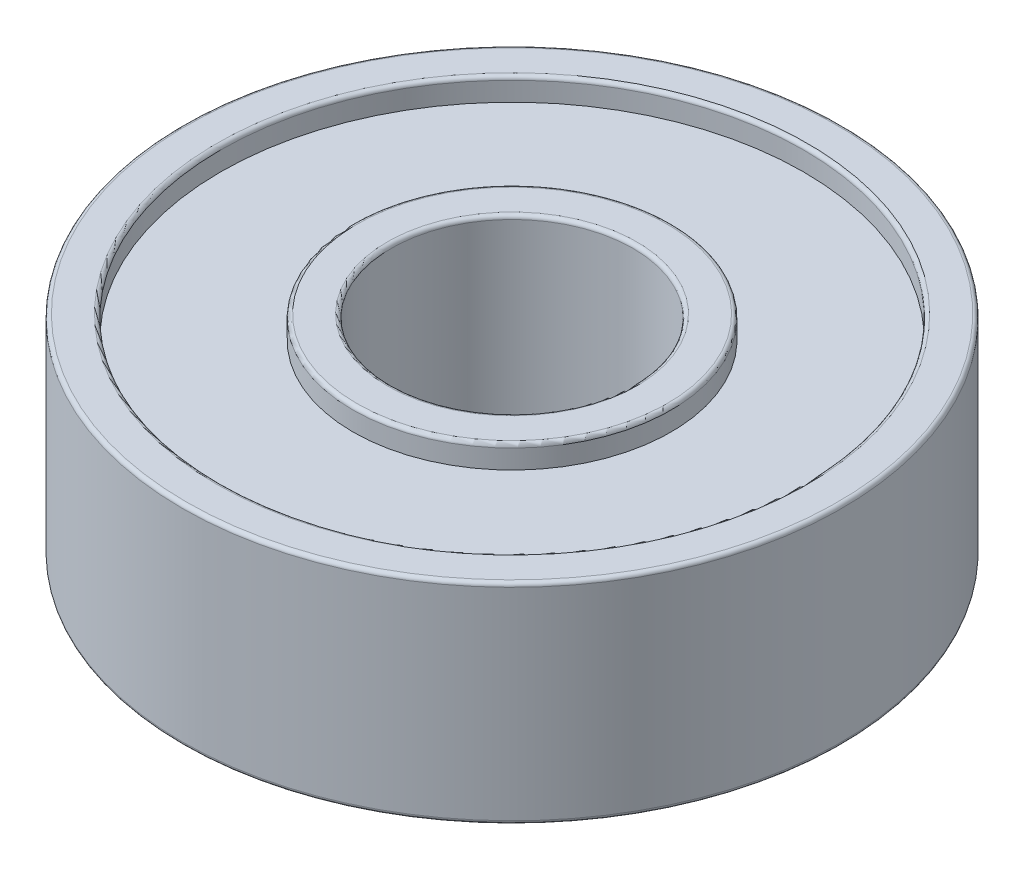
SolidWorks part; units mm, degrees
ref_plane "Front Plane" through (0, 0, 0) normal (0, 0, 1) x (1, 0, 0)
ref_plane "Top Plane" through (0, 0, 0) normal (0, 1, 0) x (1, 0, 0)
ref_plane "Right Plane" through (0, 0, 0) normal (1, 0, 0) x (0, 0, -1)
sketch "Sketch1" plane through (0, 0, 0) normal (0, 1, 0) x (1, 0, 0)
  circle A0 centre (0, 0) radius 11
  circle A1 centre (0, 0) radius 4.0386
  dimension "D1" = 22
  dimension "D2" = 8.0772
extrude "Boss-Extrude1" add sketch "Sketch1" along normal blind 3.5 and the other way blind 3.5
sketch "Sketch2" plane through (0, 3.5, 0) normal (0, 1, 0) x (1, 0, 0)
  circle A2 centre (0, 0) radius 5.3086
  circle A3 centre (0, 0) radius 5.3086
  circle A5 centre (0, 0) radius 9.73
  circle A6 centre (0, 0) radius 9.73
  dimension "D1" = 1.27
  dimension "D2" = 1.27
extrude "Cut-Extrude1" cut sketch "Sketch2" against normal blind 0.762
sketch "Sketch3" plane through (0, -3.5, 0) normal (0, -1, 0) x (1, 0, 0)
  circle A2 centre (0, 0) radius 5.3086
  circle A3 centre (0, 0) radius 5.3086
  circle A5 centre (0, 0) radius 9.73
  circle A6 centre (0, 0) radius 9.73
  dimension "D1" = 1.27
  dimension "D2" = 1.27
extrude "Cut-Extrude2" cut sketch "Sketch3" against normal blind 0.762
fillet "Fillet1" radius 0.127 8 edges at (0, -3.5, 4.0386) (0, 3.5, 4.0386) (0, -3.5, -5.3086) (0, -3.5, -9.73) (0, -3.5, 11) (0, 3.5, 5.3086) (0, 3.5, 9.73) (0, 3.5, 11)
sketch "Sketch4" plane through (0, -2.738, 0) normal (0, -1, 0) x (1, 0, 0)
  circle A0 centre (0, 0) radius 4.0386
  circle A1 centre (0, 0) radius 11
